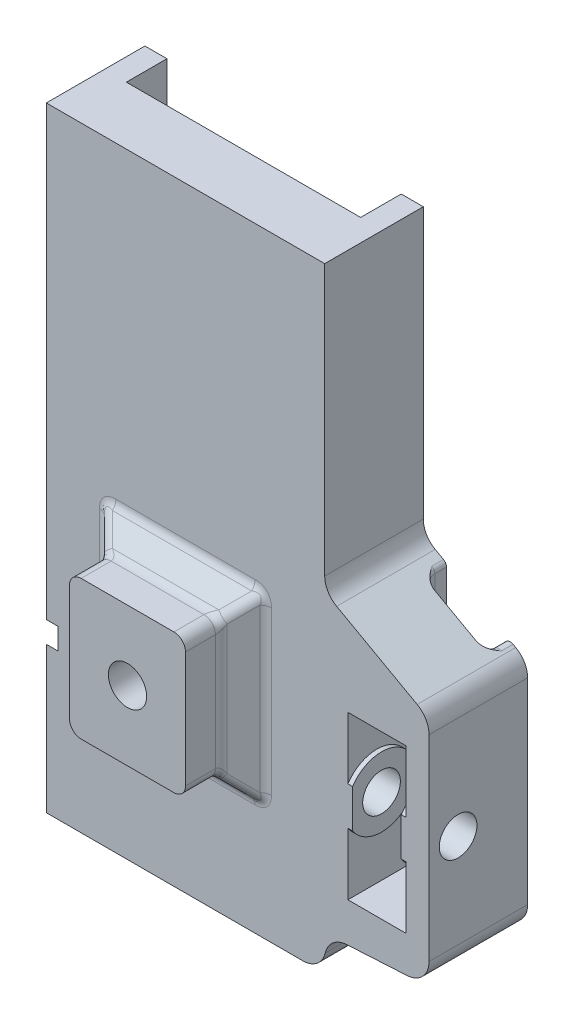
SolidWorks part; units mm, degrees
material "ABS"
ref_plane "前视基准面" through (0, 0, 0) normal (0, 0, 1) x (1, 0, 0)
ref_plane "上视基准面" through (0, 0, 0) normal (0, 1, 0) x (1, 0, 0)
ref_plane "右视基准面" through (0, 0, 0) normal (1, 0, 0) x (0, 0, -1)
other "Configuration Table"
sketch "草图1" plane through (0, 0, 0) normal (0, 0, 1) x (1, 0, 0)
  line L0 (0, 0) -> (0, 53)
  line L1 (0, 53) -> (24, 53)
  line L2 (24, 53) -> (24, 28.5)
  line L3 (24, 28.5) -> (33, 23.5)
  line L4 (33, 23.5) -> (33, 3.5)
  line L5 (33, 3.5) -> (24, 3)
  line L6 (24, 3) -> (24, 0)
  line L7 (24, 0) -> (0, 0)
  line L9 (26, 20.5) -> (31, 20.5)
  line L10 (26, 20.5) -> (26, 6.5)
  line L11 (26, 6.5) -> (31, 6.5)
  line L12 (31, 20.5) -> (31, 6.5)
  circle A0 centre (12, 18) radius 1.65
  dimension "D12" = 3.3
  dimension "D13" = 12
  dimension "D14" = 18
  dimension "D1" = 53
  dimension "D2" = 24
  dimension "D3" = 9
  dimension "D4" = 3
  dimension "D5" = 20
  dimension "D6" = 24.5
  dimension "D7" = 29.5
  dimension "D8" = 5
  dimension "D9" = 14
  dimension "D10" = 2
  dimension "D11" = 3
extrude "凸台-拉伸1" add sketch "草图1" along normal blind 8.5
sketch "草图2" plane through (0, 53, 0) normal (0, 1, 0) x (1, 0, 0)
  line L0 (24, 0) -> (0, 0) construction
  line L1 (1.9, 0) -> (22.1, 0)
  line L2 (1.9, 0) -> (1.9, -3.5)
  line L3 (1.9, -3.5) -> (22.1, -3.5)
  line L4 (22.1, 0) -> (22.1, -3.5)
  line L5 (0, -8.5) -> (0, 0) construction
  dimension "D1" = 3.5
  dimension "D2" = 1.9
  dimension "D3" = 20.2
extrude "切除-拉伸1" cut sketch "草图2" against normal offset from surface (50.1 mm away) 2.9 up to face at (12, 0, 4.25)
sketch "草图3" plane through (33, 0, 0) normal (1, 0, 0) x (0, 0, -1)
  line L0 (-8.5, 3.5) -> (-8.5, 23.5) construction
  circle A0 centre (-6, 13.5) radius 1.625
  dimension "D1" = 3.25
  dimension "D2" = 2.5
  dimension "D3" = 7
extrude "切除-拉伸2" cut sketch "草图3" against normal up to surface (7 mm away) up to face at (26, 13.5, 4.25)
sketch "草图4" plane through (26, 0, 0) normal (1, 0, 0) x (0, 0, -1)
  circle A0 centre (-6, 13.5) radius 1
  dimension "D1" = 2
extrude "切除-拉伸3" cut sketch "草图4" against normal up to surface (3.9 mm away) up to face at (22.1, 27.95, 1.75)
sketch "草图5" plane through (26, 0, 0) normal (1, 0, 0) x (0, 0, -1)
  line L0 (-8.5, 20.5) -> (-8.5, 6.5) construction
  line L1 (-8.5, 15.1583) -> (-8.5, 11.8417)
  circle A0 centre (-6, 13.5) radius 1 construction
  circle A1 centre (-6, 13.5) radius 1
  arc A2 (-8.5, 11.8417) -> (-8.5, 15.1583) centre (-6, 13.5) ccw
  dimension "D1" = 6
extrude "凸台-拉伸2" add sketch "草图5" along normal blind 0.4
sketch "草图6" plane through (31, 0, 0) normal (-1, 0, 0) x (0, 0, 1)
  line L1 (8.5, 11.8417) -> (8.5, 15.1583)
  line L2 (8.5, 11.8417) -> (8.5, 15.1583)
  circle A0 centre (6, 13.5) radius 1.625 construction
  arc A1 (8.5, 15.1583) -> (8.5, 11.8417) centre (6, 13.5) ccw
  arc A2 (8.5, 15.1583) -> (8.5, 11.8417) centre (6, 13.5) ccw
  circle A3 centre (6, 13.5) radius 1.625
  dimension "D1" = 0
extrude "凸台-拉伸3" add sketch "草图6" along normal blind 0.4
fillet "圆角1" radius 2 1 edges at (24, 3, 4.25)
fillet "圆角2" radius 2 4 edges at (24, 0, 4.25) (33, 3.5, 4.25) (33, 23.5, 4.25) (24, 28.5, 4.25)
sketch "草图7" plane through (33, 0, 0) normal (1, 0, 0) x (0, 0, -1)
  circle A0 centre (-6, 13.5) radius 1.625 construction
  circle A1 centre (-6, 13.5) radius 1.625
extrude "切除-拉伸4" cut sketch "草图7" against normal through all
sketch "草图8" plane through (0, 0, 0) normal (0, 0, -1) x (-1, 0, 0)
  line L1 (-31, 20.5) -> (-26, 20.5)
  line L2 (-31, 20.5) -> (-31, 30.7726)
  line L3 (-31, 30.7726) -> (-26, 30.7726)
  line L4 (-26, 20.5) -> (-26, 30.7726)
extrude "切除-拉伸5" cut sketch "草图8" against normal blind 2
fillet "圆角3" radius 0.5 2 edges at (31, 24.6111, 1) (26, 27.3889, 1)
fillet "圆角4" radius 1 4 edges at (31.2464, 24.1923, 2) (25.9309, 27.3483, 2) (31, 22.1307, 2) (26, 23.7973, 2)
sketch "草图9" plane through (0, 0, 8.5) normal (0, 0, 1) x (1, 0, 0)
  line L1 (7, 12) -> (17, 12)
  line L2 (7, 12) -> (7, 24)
  line L3 (7, 24) -> (17, 24)
  line L4 (17, 12) -> (17, 24)
  line L5 (7, 12) -> (17, 24) construction
  line L6 (7, 24) -> (17, 12) construction
  circle A0 centre (12, 18) radius 1.65 construction
  circle A1 centre (12, 18) radius 1.65
  dimension "D1" = 10
  dimension "D2" = 12
extrude "凸台-拉伸4" add sketch "草图9" along normal blind 5
chamfer "倒角1" distance 2 angle 45 4 edges at (12, 24, 8.5) (7, 18, 8.5) (12, 12, 8.5) (17, 18, 8.5)
fillet "圆角5" radius 1 16 edges at (12, 12, 10.5) (12, 10, 8.5) (17, 18, 10.5) (19, 18, 8.5) (18, 11, 9.5) (12, 24, 10.5) (12, 26, 8.5) (18, 25, 9.5) (5, 18, 8.5) (6, 25, 9.5) (7, 18, 10.5) (6, 11, 9.5) (7, 12, 12) (7, 24, 12) (17, 24, 12) (17, 12, 12)
sketch "Sketch1" plane through (0, 0, 0) normal (-1, 0, 0) x (0, 0, 1)
  line L1 (2.9689, 13.5) -> (4.4845, 10.875)
  line L2 (4.4845, 10.875) -> (7.5155, 10.875)
  line L3 (7.5155, 10.875) -> (9.0311, 13.5)
  line L4 (9.0311, 13.5) -> (7.5155, 16.125)
  line L5 (7.5155, 16.125) -> (4.4845, 16.125)
  line L6 (4.4845, 16.125) -> (2.9689, 13.5)
  circle A0 centre (6, 13.5) radius 2.625 construction
  dimension "D1" = 5.25
extrude "Cut-Extrude1" cut sketch "Sketch1" against normal blind 1
